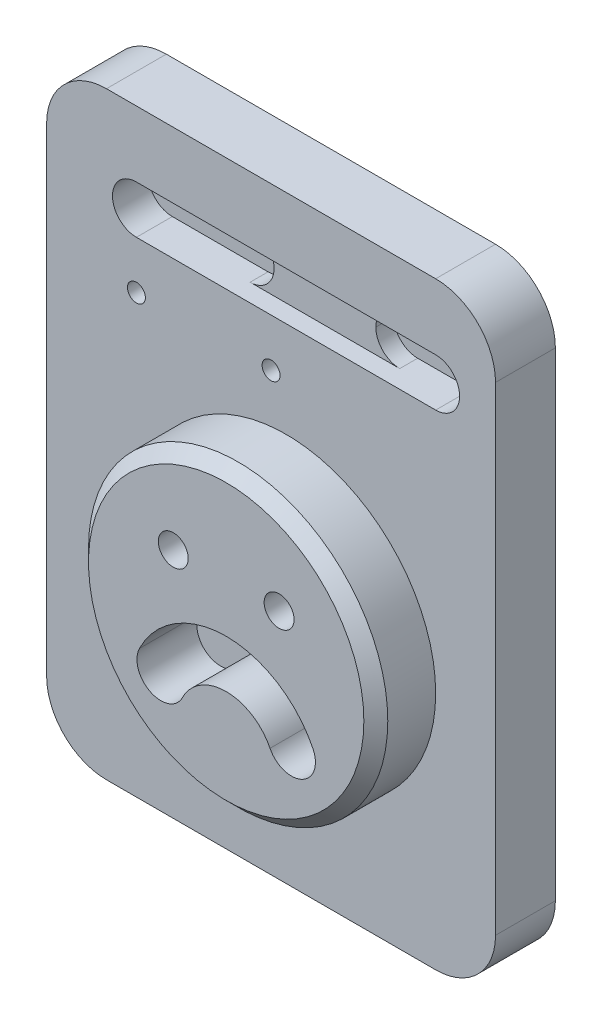
SolidWorks part; units mm, degrees
ref_plane "Front Plane" through (0, 0, 0) normal (0, 0, 1) x (1, 0, 0)
ref_plane "Top Plane" through (0, 0, 0) normal (0, 1, 0) x (1, 0, 0)
ref_plane "Right Plane" through (0, 0, 0) normal (1, 0, 0) x (0, 0, -1)
sketch "Sketch2" plane through (0, 0, 0) normal (0, 0, 1) x (1, 0, 0)
  line L1 (0, 0) -> (75, 0)
  line L2 (0, 0) -> (0, 100)
  line L3 (0, 100) -> (75, 100)
  line L4 (75, 0) -> (75, 100)
  dimension "D1" = 75
  dimension "D2" = 100
extrude "Boss-Extrude1" add sketch "Sketch2" along normal blind 10
sketch "Sketch5" plane through (0, 0, 10) normal (0, 0, 1) x (1, 0, 0)
  line L0 (75, 0) -> (75, 100) construction
  line L1 (0, 0) -> (75, 0) construction
  line L2 (40, 65) -> (40, 15) construction
  arc A0 (25.2222, 60.1647) -> (54.7778, 60.1647) centre (40, 40) ccw
  arc A5 (48.8515, 63.3806) -> (31.1485, 63.3806) centre (40, 40) ccw
  arc A6 (31.1485, 63.3806) -> (25.2222, 60.1647) centre (40, 40) ccw
  arc A7 (48.8515, 63.3806) -> (54.7778, 60.1647) centre (40, 40) cw
  dimension "D1" = 50
  dimension "D2" = 35
  dimension "D3" = 40
extrude "Boss-Extrude4" add sketch "Sketch5" along normal blind 10
sketch "Sketch6" plane through (0, 0, 20) normal (0, 0, 1) x (1, 0, 0)
  line L0 (15, 40) -> (65, 40) construction
  line L1 (40, 65) -> (40, 15) construction
  line L2 (40, 40) -> (22.3223, 57.6777) construction
  line L3 (40, 40) -> (57.6777, 57.6777)
  circle A0 centre (40, 40) radius 25 construction
  circle A1 centre (40, 40) radius 25 construction
  point P11 (31.1612, 48.8388)
  point P13 (40, 35)
  point P14 (48.8388, 48.8388)
  dimension "D1" = 45
  dimension "D2" = 45
  dimension "D3" = 5
hole_wizard "Ø5.0 (5) Diameter Hole1" positions "Sketch7" profile "Sketch8" hole size "Ø5.0" standard "AS" end condition through all
sketch "Sketch7" plane through (0, 0, 20) normal (0, 0, 1) x (1, 0, 0)
  point P0 (31.1612, 48.8388)
  point P3 (48.8388, 48.8388)
sketch "Sketch8" plane through (31.1612, 48.8388, 20) normal (1, 0, 0) x (0, -1, 0)
  line L0 (0, 0) -> (0, 20)
  line L1 (0, 20) -> (2.5, 20)
  line L2 (2.5, 20) -> (2.5, 0)
  line L5 (2.5, 0) -> (0, 0)
  line L11 (0, -6.35) -> (0, 107.95) construction
  dimension "Thru Hole Dia." = 5
  dimension "Thru Hole Depth" = 20
sketch "Sketch12" plane through (0, 0, 10) normal (0, 0, 1) x (1, 0, 0)
  line L0 (15, 85) -> (65, 85) construction
  line L1 (15, 89) -> (65, 89)
  line L2 (15, 81) -> (65, 81)
  line L3 (75, 100) -> (0, 100) construction
  line L4 (40, 65) -> (40, 96.7105) construction
  arc A0 (15, 89) -> (15, 81) centre (15, 85) ccw
  arc A1 (65, 81) -> (65, 89) centre (65, 85) ccw
  point P2 (40, 85)
  dimension "D1" = 15
  dimension "D2" = 8
  dimension "D3" = 50
extrude "Cut-Extrude1" cut sketch "Sketch12" against normal blind 6
fillet "Fillet1" radius 10 4 edges at (0, 0, 5) (75, 0, 5) (75, 100, 5) (0, 100, 5)
sketch "Sketch13" plane through (0, 0, 10) normal (0, 0, 1) x (1, 0, 0)
  line L0 (0, 73) -> (75, 73) construction
  line L1 (0, 90) -> (0, 10) construction
  line L2 (75, 10) -> (75, 90) construction
  line L3 (65, 100) -> (10, 100) construction
  point P8 (15, 73)
  point P9 (60, 73)
  point P10 (37.5, 73)
  dimension "D1" = 27
  dimension "D2" = 15
  dimension "D3" = 15
hole_wizard "Ø3.0 (3) Diameter Hole1" positions "Sketch14" profile "Sketch15" hole size "Ø3.0" standard "AS"
sketch "Sketch14" plane through (0, 0, 10) normal (0, 0, 1) x (1, 0, 0)
  line L0 (0, 73) -> (75, 73) construction
  point P0 (15, 73)
  point P3 (37.5, 73)
sketch "Sketch15" plane through (15, 73, 10) normal (1, 0, 0) x (0, -1, 0)
  line L0 (0, 0) -> (0, 10.9013)
  line L1 (0, 10.9013) -> (1.5, 10)
  line L2 (1.5, 10) -> (1.5, 0)
  line L5 (1.5, 0) -> (0, 0)
  line L10 (0, 10.9013) -> (-1.5, 10) construction
  line L11 (0, -6.35) -> (0, 107.95) construction
  dimension "Hole Dia." = 3
  dimension "Hole Depth" = 10
  dimension "Drill Angle" = 118
sketch "Sketch18" plane through (0, 0, 4) normal (0, 0, 1) x (1, 0, 0)
  line L0 (40, 89) -> (40, 81) construction
  line L1 (65, 89) -> (15, 89) construction
  line L2 (15, 81) -> (65, 81) construction
  line L4 (35, 89) -> (52, 89)
  line L5 (35, 89) -> (35, 81)
  line L6 (35, 81) -> (52, 81)
  line L7 (52, 89) -> (52, 81)
  dimension "D1" = 5
  dimension "D2" = 12
extrude "Boss-Extrude5" add sketch "Sketch18" along normal blind 3
fillet "Fillet2" radius 4 4 edges at (52, 81, 5.5) (52, 89, 5.5) (35, 81, 5.5) (35, 89, 5.5)
sketch "Sketch19" plane through (0, 0, 10) normal (0, 0, 1) x (1, 0, 0)
  line L0 (12.5994, 7.3232) -> (65.2612, 7.3232) construction
  text T0 "YAY                    NAY"
sketch "Sketch20" plane through (0, 0, 20) normal (0, 0, 1) x (1, 0, 0)
  line L0 (40, 65) -> (40, 15) construction
  line L1 (29.0891, 29.9881) -> (50.9109, 29.9881) construction
  arc A0 (29.0891, 29.9881) -> (50.9109, 29.9881) centre (40, 24.6091) cw construction
  arc A1 (54.4986, 31.7568) -> (25.5014, 31.7568) centre (40, 24.6091) ccw
  arc A2 (47.3232, 28.2194) -> (32.6768, 28.2194) centre (40, 24.6091) ccw
  arc A3 (47.3232, 28.2194) -> (54.4986, 31.7568) centre (50.9109, 29.9881) ccw
  arc A4 (25.5014, 31.7568) -> (32.6768, 28.2194) centre (29.0891, 29.9881) ccw
  circle A5 centre (40, 40) radius 25 construction
  circle A6 centre (40, 40) radius 25 construction
  point P3 (40, 36.7739)
  dimension "D1" = 4
extrude "Cut-Extrude2" cut sketch "Sketch20" against normal blind 10
chamfer "Chamfer1" distance 2 angle 45 1 edges at (65, 40, 20)
sketch "Sketch21" plane through (0, 0, 10) normal (0, 0, 1) x (1, 0, 0)
  line L1 (9.1526, 13.9473) -> (26.6691, 13.9473)
  line L2 (9.1526, 13.9473) -> (9.1526, 4.5285)
  line L3 (9.1526, 4.5285) -> (26.6691, 4.5285)
  line L4 (26.6691, 13.9473) -> (26.6691, 4.5285)
